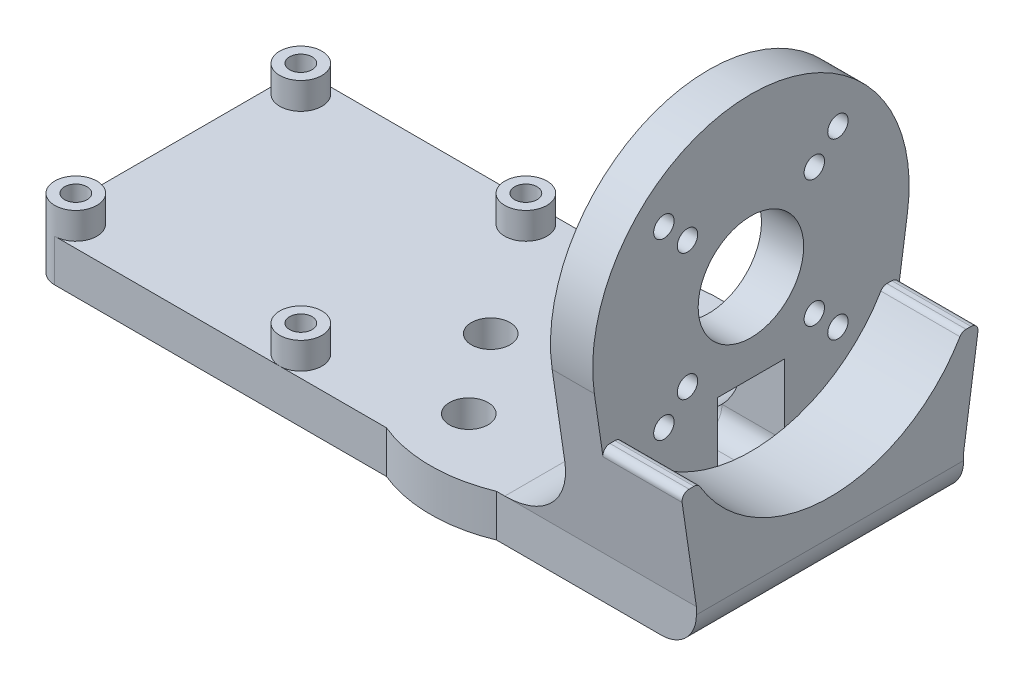
SolidWorks part; units mm, degrees
ref_plane "Front Plane" through (0, 0, 0) normal (0, 0, 1) x (1, 0, 0)
ref_plane "Top Plane" through (0, 0, 0) normal (0, 1, 0) x (1, 0, 0)
ref_plane "Right Plane" through (0, 0, 0) normal (1, 0, 0) x (0, 0, -1)
sketch "Sketch1" plane through (0, 18, 0) normal (0, 1, 0) x (1, 0, 0)
  circle A1 centre (0, 0) radius 20.55
  circle A2 centre (0, 0) radius 20.55
  dimension "D1" = 0
extrude "Boss-Extrude1" add sketch "Sketch1" along normal blind 6
sketch "Sketch12" plane through (0, 24, 0) normal (0, 1, 0) x (1, 0, 0)
  line L1 (-58, 19) -> (-20, 19)
  line L2 (-58, 19) -> (-58, -19)
  line L3 (-58, -19) -> (-20, -19)
  line L4 (-20, 19) -> (-20, -19) construction
  line L5 (-20, 19) -> (25, 19)
  line L6 (-20, 19) -> (-20, -19) construction
  line L7 (-20, -19) -> (25, -19)
  line L8 (25, 19) -> (25, -19)
  point P4 (-20, 0)
  dimension "D1" = 38
  dimension "D2" = 20
  dimension "D3" = 45
extrude "Boss-Extrude5" add sketch "Sketch12" against normal up to surface (6 mm away) contours L7 L8 L5 L1 L2 L3 up to face at (-20.55, 18, 0)
sketch "Sketch5" plane through (0, 18, 0) normal (0, 1, 0) x (1, 0, 0)
  circle A0 centre (-12, 0) radius 2.75
  circle A1 centre (-3.7082, 11.4127) radius 2.75
  circle A2 centre (9.7082, 7.0534) radius 2.75
  circle A3 centre (-3.7082, -11.4127) radius 2.75
  circle A4 centre (9.7082, -7.0534) radius 2.75
  dimension "D1" = 5.5
extrude "Cut-Extrude1" cut sketch "Sketch5" along normal up to surface (6 mm away) up to face at (-8.25, 24, 0)
fillet "Fillet3" radius 3 2 edges at (-58, 21, 19) (-58, 21, -19)
sketch "Sketch15" plane through (0, 24, 0) normal (0, 1, 0) x (1, 0, 0)
  circle A0 centre (-55, 16) radius 3
  circle A1 centre (-23, 16) radius 3
  circle A2 centre (-23, -16) radius 3
  circle A3 centre (-55, -16) radius 3
  dimension "D1" = 6
extrude "Boss-Extrude6" add sketch "Sketch15" along normal up to surface (3.8 mm away)
sketch "Sketch16" plane through (0, 27.8, 0) normal (0, 1, 0) x (1, 0, 0)
  circle A0 centre (-55, 16) radius 1.6
  circle A1 centre (-23, 16) radius 1.6
  circle A2 centre (-23, -16) radius 1.6
  circle A3 centre (-55, -16) radius 1.6
  dimension "D1" = 3.2
extrude "Cut-Extrude7" cut sketch "Sketch16" against normal blind 4.3
sketch "Sketch20" plane through (25, 0, 0) normal (1, 0, 0) x (0, 0, -1)
  line L0 (19, 24) -> (-19, 24) construction
  line L1 (-19, 24) -> (-22.2617, 46.2342)
  line L2 (19, 24) -> (22.2617, 46.2342)
  line L3 (19, 24) -> (-19, 24)
  arc A0 (22.2617, 46.2342) -> (-22.2617, 46.2342) centre (0, 49.5) ccw
  arc A1 (-22.2617, 46.2342) -> (22.2617, 46.2342) centre (0, 49.5) ccw construction
  dimension "D1" = 45
  dimension "D2" = 25.5
extrude "Boss-Extrude7" add sketch "Sketch20" against normal blind 6
sketch "Sketch22" plane through (25, 0, 0) normal (1, 0, 0) x (0, 0, -1)
  line L0 (-21.2005, 39) -> (-18.7617, 39)
  line L1 (21.2005, 39) -> (22.2617, 46.2342) construction
  line L2 (-22.2617, 46.2342) -> (-21.2005, 39) construction
  line L3 (-18.7617, 39) -> (18.7617, 39) construction
  line L4 (18.7617, 39) -> (21.2005, 39)
  line L5 (-19, 24) -> (-19, 18)
  line L6 (-19, 18) -> (19, 18)
  line L7 (19, 18) -> (19, 24)
  line L8 (19, 24) -> (22.2617, 46.2342)
  line L9 (-22.2617, 46.2342) -> (-19, 24)
  line L10 (-19, 24) -> (-19, 18)
  line L11 (-19, 18) -> (19, 18)
  line L12 (19, 18) -> (19, 24)
  line L13 (19, 24) -> (21.2005, 39)
  line L14 (-21.2005, 39) -> (-19, 24)
  arc A0 (-18.7617, 39) -> (18.7617, 39) centre (0, 49.5) ccw
  arc A1 (22.2617, 46.2342) -> (-22.2617, 46.2342) centre (0, 49.5) ccw
  arc A2 (22.2617, 46.2342) -> (-22.2617, 46.2342) centre (0, 49.5) ccw construction
  arc A3 (18.7617, 39) -> (-18.7617, 39) centre (0, 49.5) ccw construction
  point P11 (0, 39)
  dimension "D2" = 43
  dimension "D3" = 15
  dimension "D1" = 0
extrude "Boss-Extrude8" add sketch "Sketch22" along normal blind 11.25
fillet "Fillet4" radius 1 4 edges at (30.625, 39, -21.2005) (30.625, 39, -18.7617) (30.625, 39, 18.7617) (30.625, 39, 21.2005)
fillet "Fillet5" radius 5 1 edges at (36.25, 18, 0)
fillet "Fillet6" radius 10 1 edges at (19, 24, 0)
sketch "Sketch24" plane through (25, 0, 0) normal (-1, 0, 0) x (0, 0, 1)
  line L0 (-16, 24) -> (16, 24) construction
  line L1 (-4.75, 37) -> (4.75, 37)
  line L2 (-4.75, 37) -> (-4.75, 24)
  line L3 (-4.75, 24) -> (4.75, 24)
  line L4 (4.75, 37) -> (4.75, 24)
  arc A0 (2.5, 35.2029) -> (2.5, 33.2029) centre (2.5, 34.2029) ccw construction
  arc A1 (2.5, 33.2029) -> (2.5, 35.2029) centre (2.5, 34.2029) ccw construction
  arc A2 (0, 35) -> (0, 33) centre (0, 34) ccw construction
  arc A3 (0, 33) -> (0, 35) centre (0, 34) ccw construction
  arc A4 (-2.5, 35.2029) -> (-2.5, 33.2029) centre (-2.5, 34.2029) ccw construction
  arc A5 (-2.5, 33.2029) -> (-2.5, 35.2029) centre (-2.5, 34.2029) ccw construction
  arc A6 (-12.3744, 62.8744) -> (-12.3744, 60.8744) centre (-12.3744, 61.8744) ccw construction
  arc A7 (-12.3744, 60.8744) -> (-12.3744, 62.8744) centre (-12.3744, 61.8744) ccw construction
  arc A8 (-9.0156, 59.5156) -> (-9.0156, 57.5156) centre (-9.0156, 58.5156) ccw construction
  arc A9 (-9.0156, 57.5156) -> (-9.0156, 59.5156) centre (-9.0156, 58.5156) ccw construction
  arc A10 (12.3744, 62.8744) -> (12.3744, 60.8744) centre (12.3744, 61.8744) ccw construction
  arc A11 (12.3744, 60.8744) -> (12.3744, 62.8744) centre (12.3744, 61.8744) ccw construction
  arc A12 (9.0156, 59.5156) -> (9.0156, 57.5156) centre (9.0156, 58.5156) ccw construction
  arc A13 (9.0156, 57.5156) -> (9.0156, 59.5156) centre (9.0156, 58.5156) ccw construction
  arc A14 (12.3744, 38.1256) -> (12.3744, 36.1256) centre (12.3744, 37.1256) ccw construction
  arc A15 (12.3744, 36.1256) -> (12.3744, 38.1256) centre (12.3744, 37.1256) ccw construction
  arc A16 (9.0156, 41.4844) -> (9.0156, 39.4844) centre (9.0156, 40.4844) ccw construction
  arc A17 (9.0156, 39.4844) -> (9.0156, 41.4844) centre (9.0156, 40.4844) ccw construction
  arc A18 (-12.3744, 38.1256) -> (-12.3744, 36.1256) centre (-12.3744, 37.1256) ccw construction
  arc A19 (-12.3744, 36.1256) -> (-12.3744, 38.1256) centre (-12.3744, 37.1256) ccw construction
  arc A20 (-9.0156, 41.4844) -> (-9.0156, 39.4844) centre (-9.0156, 40.4844) ccw construction
  arc A21 (-9.0156, 39.4844) -> (-9.0156, 41.4844) centre (-9.0156, 40.4844) ccw construction
  arc A22 (2.5, 35.2029) -> (2.5, 33.2029) centre (2.5, 34.2029) ccw construction
  arc A23 (2.5, 33.2029) -> (2.5, 35.2029) centre (2.5, 34.2029) ccw construction
  arc A24 (0, 35) -> (0, 33) centre (0, 34) ccw construction
  arc A25 (0, 33) -> (0, 35) centre (0, 34) ccw construction
  arc A26 (-2.5, 35.2029) -> (-2.5, 33.2029) centre (-2.5, 34.2029) ccw construction
  arc A27 (-2.5, 33.2029) -> (-2.5, 35.2029) centre (-2.5, 34.2029) ccw construction
  arc A28 (-12.3744, 62.8744) -> (-12.3744, 60.8744) centre (-12.3744, 61.8744) ccw construction
  arc A29 (-12.3744, 60.8744) -> (-12.3744, 62.8744) centre (-12.3744, 61.8744) ccw construction
  arc A30 (-9.0156, 59.5156) -> (-9.0156, 57.5156) centre (-9.0156, 58.5156) ccw construction
  arc A31 (-9.0156, 57.5156) -> (-9.0156, 59.5156) centre (-9.0156, 58.5156) ccw construction
  arc A32 (12.3744, 62.8744) -> (12.3744, 60.8744) centre (12.3744, 61.8744) ccw construction
  arc A33 (12.3744, 60.8744) -> (12.3744, 62.8744) centre (12.3744, 61.8744) ccw construction
  arc A34 (9.0156, 59.5156) -> (9.0156, 57.5156) centre (9.0156, 58.5156) ccw construction
  arc A35 (9.0156, 57.5156) -> (9.0156, 59.5156) centre (9.0156, 58.5156) ccw construction
  arc A36 (12.3744, 38.1256) -> (12.3744, 36.1256) centre (12.3744, 37.1256) ccw construction
  arc A37 (12.3744, 36.1256) -> (12.3744, 38.1256) centre (12.3744, 37.1256) ccw construction
  arc A38 (9.0156, 41.4844) -> (9.0156, 39.4844) centre (9.0156, 40.4844) ccw construction
  arc A39 (9.0156, 39.4844) -> (9.0156, 41.4844) centre (9.0156, 40.4844) ccw construction
  arc A40 (-12.3744, 38.1256) -> (-12.3744, 36.1256) centre (-12.3744, 37.1256) ccw construction
  arc A41 (-12.3744, 36.1256) -> (-12.3744, 38.1256) centre (-12.3744, 37.1256) ccw construction
  arc A42 (-9.0156, 41.4844) -> (-9.0156, 39.4844) centre (-9.0156, 40.4844) ccw construction
  arc A43 (-9.0156, 39.4844) -> (-9.0156, 41.4844) centre (-9.0156, 40.4844) ccw construction
  arc A44 (22.2617, 46.2342) -> (-22.2617, 46.2342) centre (0, 49.5) ccw construction
  arc A45 (22.2617, 46.2342) -> (-22.2617, 46.2342) centre (0, 49.5) ccw construction
  circle A46 centre (0, 49.5) radius 7.5
  point P44 (0, 24)
  dimension "D1" = 15
  dimension "D2" = 9.5
  dimension "D3" = 13
extrude "Cut-Extrude8" cut sketch "Sketch24" along normal through all
sketch "Sketch25" plane through (25, 0, 0) normal (1, 0, 0) x (0, 0, -1)
  arc A0 (-12.3744, 60.8744) -> (-12.3744, 62.8744) centre (-12.3744, 61.8744) ccw construction
  arc A1 (-12.3744, 62.8744) -> (-12.3744, 60.8744) centre (-12.3744, 61.8744) ccw construction
  arc A2 (12.3744, 60.8744) -> (12.3744, 62.8744) centre (12.3744, 61.8744) ccw construction
  arc A3 (12.3744, 62.8744) -> (12.3744, 60.8744) centre (12.3744, 61.8744) ccw construction
  arc A4 (9.0156, 57.5156) -> (9.0156, 59.5156) centre (9.0156, 58.5156) ccw construction
  arc A5 (9.0156, 59.5156) -> (9.0156, 57.5156) centre (9.0156, 58.5156) ccw construction
  arc A6 (12.3744, 36.1256) -> (12.3744, 38.1256) centre (12.3744, 37.1256) ccw construction
  arc A7 (12.3744, 38.1256) -> (12.3744, 36.1256) centre (12.3744, 37.1256) ccw construction
  arc A8 (9.0156, 39.4844) -> (9.0156, 41.4844) centre (9.0156, 40.4844) ccw construction
  arc A9 (9.0156, 41.4844) -> (9.0156, 39.4844) centre (9.0156, 40.4844) ccw construction
  arc A10 (-12.3744, 36.1256) -> (-12.3744, 38.1256) centre (-12.3744, 37.1256) ccw construction
  arc A11 (-12.3744, 38.1256) -> (-12.3744, 36.1256) centre (-12.3744, 37.1256) ccw construction
  arc A12 (-9.0156, 39.4844) -> (-9.0156, 41.4844) centre (-9.0156, 40.4844) ccw construction
  arc A13 (-9.0156, 41.4844) -> (-9.0156, 39.4844) centre (-9.0156, 40.4844) ccw construction
  arc A14 (-9.0156, 57.5156) -> (-9.0156, 59.5156) centre (-9.0156, 58.5156) ccw construction
  arc A15 (-9.0156, 59.5156) -> (-9.0156, 57.5156) centre (-9.0156, 58.5156) ccw construction
  arc A16 (-12.3744, 60.8744) -> (-12.3744, 62.8744) centre (-12.3744, 61.8744) ccw construction
  arc A17 (-12.3744, 62.8744) -> (-12.3744, 60.8744) centre (-12.3744, 61.8744) ccw construction
  arc A18 (12.3744, 60.8744) -> (12.3744, 62.8744) centre (12.3744, 61.8744) ccw construction
  arc A19 (12.3744, 62.8744) -> (12.3744, 60.8744) centre (12.3744, 61.8744) ccw construction
  arc A20 (9.0156, 57.5156) -> (9.0156, 59.5156) centre (9.0156, 58.5156) ccw construction
  arc A21 (9.0156, 59.5156) -> (9.0156, 57.5156) centre (9.0156, 58.5156) ccw construction
  arc A22 (12.3744, 36.1256) -> (12.3744, 38.1256) centre (12.3744, 37.1256) ccw construction
  arc A23 (12.3744, 38.1256) -> (12.3744, 36.1256) centre (12.3744, 37.1256) ccw construction
  arc A24 (9.0156, 39.4844) -> (9.0156, 41.4844) centre (9.0156, 40.4844) ccw construction
  arc A25 (9.0156, 41.4844) -> (9.0156, 39.4844) centre (9.0156, 40.4844) ccw construction
  arc A26 (-12.3744, 36.1256) -> (-12.3744, 38.1256) centre (-12.3744, 37.1256) ccw construction
  arc A27 (-12.3744, 38.1256) -> (-12.3744, 36.1256) centre (-12.3744, 37.1256) ccw construction
  arc A28 (-9.0156, 39.4844) -> (-9.0156, 41.4844) centre (-9.0156, 40.4844) ccw construction
  arc A29 (-9.0156, 41.4844) -> (-9.0156, 39.4844) centre (-9.0156, 40.4844) ccw construction
  arc A30 (-9.0156, 57.5156) -> (-9.0156, 59.5156) centre (-9.0156, 58.5156) ccw construction
  arc A31 (-9.0156, 59.5156) -> (-9.0156, 57.5156) centre (-9.0156, 58.5156) ccw construction
  circle A32 centre (12.3744, 61.8744) radius 1.45
  circle A33 centre (9.0156, 58.5156) radius 1.45
  circle A34 centre (-9.0156, 58.5156) radius 1.45
  circle A35 centre (-12.3744, 61.8744) radius 1.45
  circle A36 centre (-9.0156, 40.4844) radius 1.45
  circle A37 centre (-12.3744, 37.1256) radius 1.45
  circle A38 centre (9.0156, 40.4844) radius 1.45
  circle A39 centre (12.3744, 37.1256) radius 1.45
  dimension "D1" = 2.9
extrude "Cut-Extrude9" cut sketch "Sketch25" against normal up to surface (6 mm away) up to face at (19, 41.0293, 0)
fillet "Fillet7" radius 3 3 edges at (18.1052, 24, -4.75) (18.1052, 24, 4.75) (25, 24, 0)
equation "\"M5_CLRNCE\"=5.5"
equation "\"FLANGE_TH\"=6"
equation "\"D1@Boss-Extrude1\"=\"FLANGE_TH\""
equation "\"D1@Sketch5\"=\"M5_CLRNCE\""
equation "\"MOTOR_OFFSET\"= 45"
equation "\"MOTOR_H_OFFSET\"=0"
equation "\"D1\"= \"MOTOR_H_OFFSET\""
equation "\"M2.5_INSERT_DIAM\"=3.2"
equation "\"D1@Sketch16\"=\"M2.5_INSERT_DIAM\""
equation "\"M2.5_INSERT_DEPTH\"=4.3"
equation "\"D1@Cut-Extrude7\"=\"M2.5_INSERT_DEPTH\""
equation "\"D2@Sketch20\"=45/2+3"
equation "\"D1@Boss-Extrude8\"=22.5/2"
equation "\"M2.5_CLRNCE\"=2.9"
equation "\"D1@Sketch25\"=\"M2.5_CLRNCE\""
